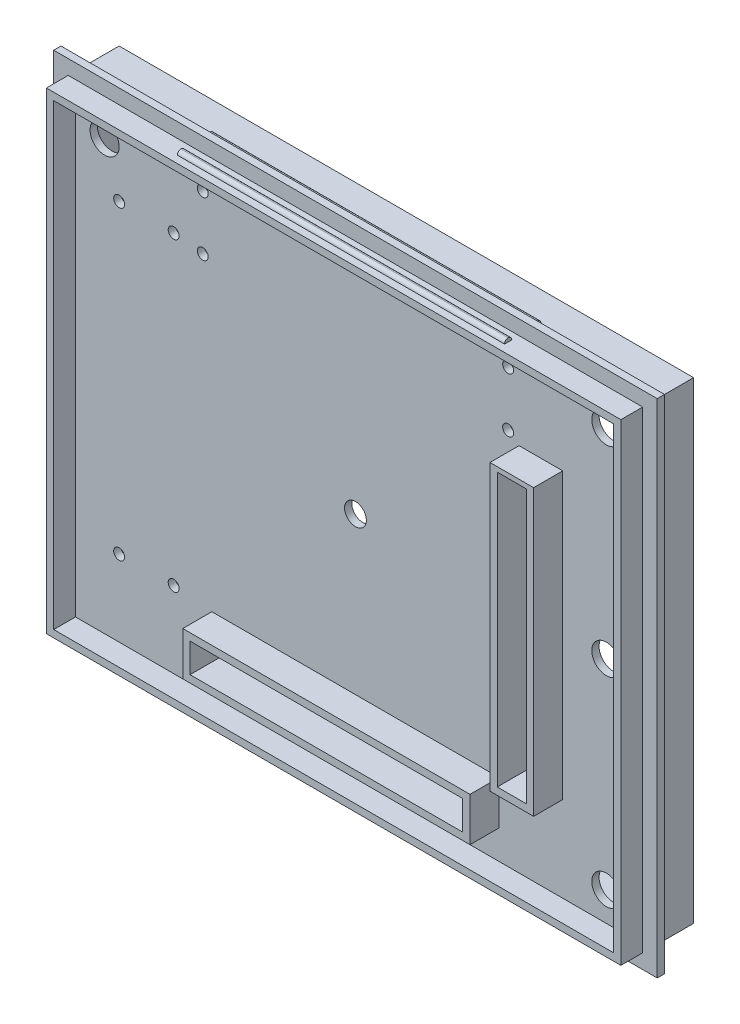
SolidWorks part; units mm, degrees
ref_plane "정면" through (0, 0, 0) normal (0, 0, 1) x (1, 0, 0)
ref_plane "윗면" through (0, 0, 0) normal (0, 1, 0) x (1, 0, 0)
ref_plane "우측면" through (0, 0, 0) normal (1, 0, 0) x (0, 0, -1)
sketch "스케치1" plane through (0, 0, 0) normal (0, 0, 1) x (1, 0, 0)
  line L1 (-83, -69) -> (83, -69)
  line L2 (-83, -69) -> (-83, 69)
  line L3 (-83, 69) -> (83, 69)
  line L4 (83, -69) -> (83, 69)
  line L5 (-83, -69) -> (83, 69) construction
  line L6 (-83, 69) -> (83, -69) construction
  point P0 (0, 0)
  dimension "D1" = 138
  dimension "D2" = 166
extrude "보스-돌출1" add sketch "스케치1" along normal blind 2
sketch "스케치2" plane through (0, 0, 2) normal (0, 0, 1) x (1, 0, 0)
  line L1 (78, -64) -> (-78, -64)
  line L2 (78, -64) -> (78, 64)
  line L3 (78, 64) -> (-78, 64)
  line L4 (-78, -64) -> (-78, 64)
  line L5 (78, -64) -> (-78, 64) construction
  line L6 (78, 64) -> (-78, -64) construction
  point P0 (0, 0)
  dimension "D1" = 156
  dimension "D2" = 128
extrude "돌출-얇게2" add sketch "스케치2" along normal blind 6 and the other way blind 14 thin thin type mid plane wall 2
sketch "스케치3" plane through (0, 0, 2) normal (0, 0, 1) x (1, 0, 0)
  line L0 (-77, 63) -> (-77, -63) construction
  line L1 (-77, -63) -> (77, -63) construction
  line L2 (0, 0) -> (-60.4679, 0) construction
  circle A0 centre (-65, -42) radius 1.5
  circle A1 centre (-50, -42) radius 1.5
  circle A2 centre (-65, 42) radius 1.5
  circle A3 centre (-50, 42) radius 1.5
  dimension "D1" = 12
  dimension "D2" = 21
  dimension "D3" = 15
extrude "보스-돌출2" add sketch "스케치3" along normal blind 5
sketch "스케치4" plane through (0, 0, 2) normal (0, 0, 1) x (1, 0, 0)
  line L0 (-77, 63) -> (-77, -63) construction
  line L1 (77, 63) -> (-77, 63) construction
  circle A0 centre (-42, 56) radius 1.5
  circle A1 centre (-42, 41) radius 1.5
  dimension "D1" = 35
  dimension "D2" = 7
  dimension "15" = 15
sketch "스케치5" plane through (0, 0, 2) normal (0, 0, 1) x (1, 0, 0)
  line L0 (0, 0) -> (0, 44.9945) construction
  line L1 (77, -63) -> (77, 63) construction
  line L2 (77, 63) -> (-77, 63) construction
  circle A0 centre (42, 56) radius 1.5
  circle A1 centre (42, 41) radius 1.5
  dimension "D1" = 3
  dimension "D3" = 7
  dimension "D4" = 35
  dimension "D5" = 3
  dimension "D6" = 15
  dimension "D2" = 35
extrude "보스-돌출3" add sketch "스케치5" along normal blind 5 contours A1 | A0
extrude "보스-돌출4" add sketch "스케치4" along normal blind 5 contours A1 | A0
sketch "스케치6" plane through (0, 0, 2) normal (0, 0, 1) x (1, 0, 0)
  line L0 (-77, -63) -> (77, -63) construction
  line L1 (-37.5, -53) -> (37.5, -53)
  line L2 (-37.5, -53) -> (-37.5, -55)
  line L3 (-37.5, -55) -> (37.5, -55)
  line L4 (37.5, -53) -> (37.5, -55)
  line L5 (-37.5, -53) -> (37.5, -55) construction
  line L6 (-37.5, -55) -> (37.5, -53) construction
  line L7 (77, -63) -> (77, 63) construction
  line L8 (37.5, -43) -> (-37.5, -43)
  line L9 (37.5, -43) -> (37.5, -45)
  line L10 (37.5, -45) -> (-37.5, -45)
  line L11 (-37.5, -43) -> (-37.5, -45)
  line L12 (37.5, -43) -> (-37.5, -45) construction
  line L13 (37.5, -45) -> (-37.5, -43) construction
  line L18 (47, -37.5) -> (45, -37.5)
  line L19 (47, -37.5) -> (47, 37.5)
  line L20 (47, 37.5) -> (45, 37.5)
  line L21 (45, -37.5) -> (45, 37.5)
  line L22 (47, -37.5) -> (45, 37.5) construction
  line L23 (47, 37.5) -> (45, -37.5) construction
  line L26 (57, -37.5) -> (55, -37.5)
  line L27 (57, -37.5) -> (57, 37.5)
  line L28 (57, 37.5) -> (55, 37.5)
  line L29 (55, -37.5) -> (55, 37.5)
  line L30 (57, -37.5) -> (55, 37.5) construction
  line L31 (57, 37.5) -> (55, -37.5) construction
  point P0 (0, -54)
  point P8 (0, -44)
  point P14 (46, 0)
  point P21 (77, 0)
  point P24 (56, 0)
  dimension "D1" = 8
  dimension "D2" = 2
  dimension "D3" = 75
  dimension "D4" = 0
  dimension "D5" = 8
  dimension "D6" = 2
  dimension "D7" = 30
  dimension "D8" = 2
  dimension "D9" = 75
  dimension "D10" = 0
  dimension "D11" = 8
  dimension "D12" = 2
extrude "보스-돌출5" add sketch "스케치6" along normal blind 8
sketch "스케치9" plane through (0, -65, 0) normal (0, -1, 0) x (1, 0, 0)
  line L0 (79, 2) -> (-79, 2) construction
  line L1 (-45, 6) -> (45, 6)
  line L2 (-45, 6) -> (-45, 4)
  line L3 (-45, 4) -> (45, 4)
  line L4 (45, 6) -> (45, 4)
  line L5 (-45, 6) -> (45, 4) construction
  line L6 (-45, 4) -> (45, 6) construction
  point P0 (0, 5)
  dimension "D1" = 90
  dimension "D2" = 0
  dimension "D3" = 2
  dimension "D4" = 3
extrude "보스-돌출6" add sketch "스케치9" along normal blind 1
sketch "스케치11" plane through (0, 65, 0) normal (0, 1, 0) x (1, 0, 0)
  line L0 (-79, -2) -> (79, -2) construction
  line L1 (-45, -6) -> (45, -6)
  line L2 (-45, -6) -> (-45, -4)
  line L3 (-45, -4) -> (45, -4)
  line L4 (45, -6) -> (45, -4)
  line L5 (-45, -6) -> (45, -4) construction
  line L6 (-45, -4) -> (45, -6) construction
  point P0 (0, -5)
  dimension "D1" = 90
  dimension "D2" = 0
  dimension "D3" = 2
  dimension "D4" = 3
fillet "필렛1" radius 1 2 edges at (0, -66, 4) (0, -66, 6)
extrude "보스-돌출7" add sketch "스케치11" along normal blind 1
fillet "필렛2" radius 1 2 edges at (0, 66, 4) (0, 66, 6)
pattern_linear "선형 패턴1" count 2 spacing 8 along (0, 0, -1) of face at (0, -65.6036, 5.6036) of face at (0, -65.6036, 4.3964) of face at (-45, -65.4714, 5) of face at (45, -65.4714, 5)
pattern_linear "선형 패턴2" count 2 spacing 8 along (0, 0, -1) of face at (0, 65.6036, 4.3964) of face at (0, 65.6036, 5.6036) of face at (45, 65.4714, 5) of face at (-45, 65.4714, 5)
sketch "스케치12" plane through (0, 0, 2) normal (0, 0, 1) x (1, 0, 0)
  line L1 (-37.5, -43) -> (-39.5, -43)
  line L2 (-37.5, -43) -> (-37.5, -55)
  line L3 (-37.5, -55) -> (-39.5, -55)
  line L4 (-39.5, -43) -> (-39.5, -55)
  line L5 (37.5, -43) -> (39.5, -43)
  line L6 (37.5, -43) -> (37.5, -55)
  line L7 (37.5, -55) -> (39.5, -55)
  line L8 (39.5, -43) -> (39.5, -55)
  line L9 (57, -37.5) -> (45, -37.5)
  line L10 (57, -37.5) -> (57, -39.5)
  line L11 (57, -39.5) -> (45, -39.5)
  line L12 (45, -37.5) -> (45, -39.5)
  line L13 (45, 37.5) -> (57, 37.5)
  line L14 (45, 37.5) -> (45, 38.8)
  line L15 (45, 38.8) -> (57, 38.8)
  line L16 (57, 37.5) -> (57, 38.8)
  dimension "D1" = 2
  dimension "D2" = 2
  dimension "D3" = 2
  dimension "D4" = 1.3
extrude "보스-돌출8" add sketch "스케치12" along normal blind 8
extrude "컷-돌출2" cut sketch "스케치5<4>" against normal through all both and the other way through all
sketch "스케치5<4>" plane through (0, 0, 2) normal (0, 0, 1) x (1, 0, 0) same geometry as "스케치5"
extrude "컷-돌출3" cut sketch "스케치4<3>" against normal through all both and the other way through all
sketch "스케치4<3>" plane through (0, 0, 2) normal (0, 0, 1) x (1, 0, 0) same geometry as "스케치4"
extrude "컷-돌출4" cut sketch "스케치3<2>" against normal through all both and the other way through all
sketch "스케치3<2>" plane through (0, 0, 2) normal (0, 0, 1) x (1, 0, 0) same geometry as "스케치3"
sketch "스케치13" plane through (0, 0, 2) normal (0, 0, 1) x (1, 0, 0)
  line L0 (-77, 63) -> (77, 63) construction
  line L2 (-77, -63) -> (-77, 63) construction
  line L3 (0, 0) -> (0, 42.4509) construction
  line L4 (0, 0) -> (36.2903, 0) construction
  circle A0 centre (0, 0) radius 3
  circle A1 centre (-69, 55) radius 4
  circle A2 centre (69, 55) radius 4
  circle A3 centre (69, -55) radius 4
  circle A4 centre (69, 0) radius 4
  dimension "D1" = 8
  dimension "D2" = 8
  dimension "D3" = 8
extrude "컷-돌출5" cut sketch "스케치13" against normal through all
